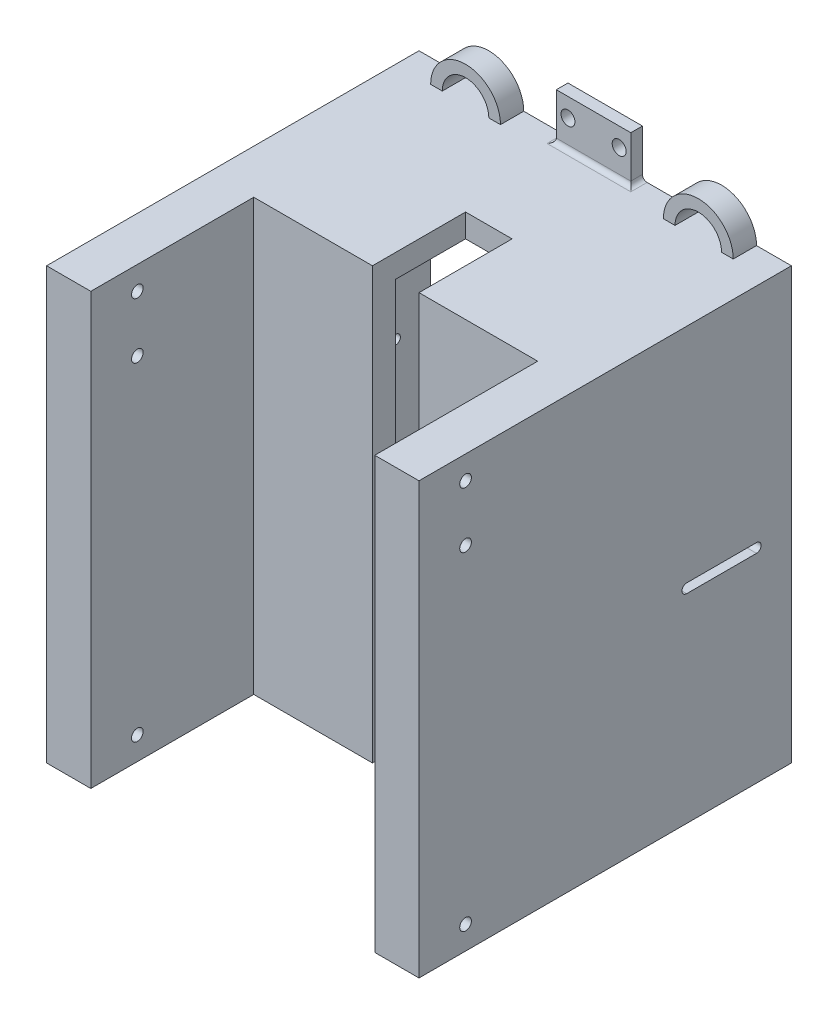
SolidWorks part; units mm, degrees
ref_plane "前基準面" through (0, 0, 0) normal (0, 0, 1) x (1, 0, 0)
ref_plane "上基準面" through (0, 0, 0) normal (0, 1, 0) x (1, 0, 0)
ref_plane "右基準面" through (0, 0, 0) normal (1, 0, 0) x (0, 0, -1)
ref_axis "基準軸1" through (0, -55, 0) along (0, 1, 0)
ref_axis "基準軸2" through (-88.99, 0, 0) along (1, 0, 0)
ref_axis "基準軸3" through (0, 0, 55) along (0, 0, -1)
sketch "草圖1" plane through (0, 0, 0) normal (0, 0, 1) x (1, 0, 0)
  line L1 (-160, -185) -> (0, -185)
  line L2 (-160, -185) -> (-160, 0)
  line L3 (-160, 0) -> (0, 0)
  line L4 (0, -185) -> (0, 0)
  dimension "D1" = 160
  dimension "D2" = 185
extrude "填料-伸長1" add sketch "草圖1" along normal blind 10
sketch "草圖2" plane through (0, 0, 0) normal (0, 0, -1) x (-1, 0, 0)
  line L0 (160, -185) -> (0, -185) construction
  line L2 (0, 0) -> (0, -185)
  line L3 (0, -185) -> (5, -185)
  line L4 (5, -10) -> (5, -185)
  line L5 (55, 0) -> (-55, 0) construction
  line L7 (160, 0) -> (160, -185)
  line L8 (160, -185) -> (155, -185)
  line L9 (155, -10) -> (155, -185)
  line L10 (160, 0) -> (160, -185) construction
  line L11 (5, -10) -> (155, -10)
  line L12 (0, 0) -> (160, 0)
  dimension "D1" = 5
  dimension "D2" = 5
  dimension "D3" = 10
extrude "填料-伸長2" add sketch "草圖2" along normal blind 80
sketch "草圖14" plane through (0, 0, 0) normal (0, 1, 0) x (1, 0, 0)
  line L0 (-80, -10) -> (-80, 74.8376) construction
  line L1 (0, -10) -> (-160, -10) construction
  line L4 (-70, -20) -> (-70, 30)
  line L5 (-70, 30) -> (-90, 30)
  line L6 (-90, -20) -> (-90, 30)
  line L10 (-90, -20) -> (-70, -20)
  point P8 (-80, 30)
  dimension "D1" = 10
  dimension "D2" = 40
  dimension "D3" = 20
extrude "除料-伸長4" cut sketch "草圖14" against normal through all
sketch "草圖16" plane through (0, 0, -80) normal (0, 0, -1) x (-1, 0, 0)
  line L0 (160, 0) -> (0, 0) construction
  line L1 (96, 0) -> (64, 0)
  line L2 (96, 0) -> (96, -10) construction
  line L3 (96, -10) -> (64, -10) construction
  line L4 (64, 0) -> (64, -10) construction
  line L5 (90, -10) -> (155, -10) construction
  line L6 (80, 0) -> (80, -74.9509) construction
  line L7 (64, 0) -> (64, 20)
  line L8 (64, 20) -> (96, 20)
  line L9 (96, 20) -> (96, 0)
  dimension "D1" = 20
  dimension "D2" = 32
extrude "填料-伸長7" add sketch "草圖16" against normal blind 5
sketch "草圖18" plane through (0, 0, -80) normal (0, 0, -1) x (-1, 0, 0)
  line L0 (80, 20) -> (80, -10) construction
  line L1 (96, 20) -> (64, 20) construction
  line L2 (5, -10) -> (155, -10) construction
  line L3 (64, 4) -> (96, 4) construction
  line L4 (64, 20) -> (64, 0) construction
  line L5 (96, 0) -> (96, 20) construction
  line L6 (69, 12) -> (91, 12) construction
  circle A0 centre (69, 12) radius 3
  circle A1 centre (91, 12) radius 3
  point P15 (80, 12)
  dimension "D4" = 6
  dimension "D1" = 16
  dimension "D2" = 11
  dimension "D3" = 8
extrude "除料-伸長7" cut sketch "草圖18" against normal up to next
fillet "圓角1" radius 2 3 edges at (-64, 0, -77.5) (-80, 0, -75) (-96, 0, -77.5)
sketch "草圖21" plane through (-160, 0, 0) normal (-1, 0, 0) x (0, 0, 1)
  line L11 (10, 0) -> (80, 0)
  line L12 (80, 0) -> (80, -185)
  line L13 (80, -185) -> (10, -185)
  line L14 (10, 0) -> (10, -185) construction
  line L15 (10, 0) -> (10, -185)
  circle A1 centre (60, -10) radius 2.5
  circle A2 centre (60, -175) radius 2.5
  circle A3 centre (60, -34) radius 2.5
  dimension "D5" = 70
  dimension "D3" = 10
  dimension "D4" = 5
  dimension "D6" = 24
  dimension "D7" = 5
  dimension "D1" = 10
  dimension "D2" = 50
extrude "填料-伸長8" add sketch "草圖21" against normal up to surface (160 mm away) up to face at (0, -92.5, -35)
sketch "草圖22" plane through (-155, 0, 0) normal (1, 0, 0) x (0, 0, -1)
  line L0 (0, -97.5) -> (80, -97.5) construction
  line L1 (35, -97.5) -> (65, -97.5) construction
  line L2 (35, -95.5) -> (65, -95.5)
  line L3 (35, -99.5) -> (65, -99.5)
  line L4 (0, -10) -> (0, -185)
  line L5 (0, -185) -> (80, -185)
  line L6 (80, -185) -> (80, -10)
  line L7 (80, -10) -> (0, -10)
  line L8 (0, -10) -> (0, -185) construction
  line L9 (0, -185) -> (80, -185) construction
  line L10 (80, -185) -> (80, -10) construction
  line L11 (80, -10) -> (0, -10) construction
  arc A0 (35, -95.5) -> (35, -99.5) centre (35, -97.5) ccw
  arc A1 (65, -99.5) -> (65, -95.5) centre (65, -97.5) ccw
  point P8 (50, -97.5)
  dimension "D3" = 2
  dimension "D2" = 30
  dimension "D4" = 30
  dimension "D1" = 0
extrude "除料-伸長9" cut sketch "草圖22" against normal through all both and the other way through all contours L3 A1 L2 A0
sketch "草圖23" plane through (0, 0, 0) normal (0, 1, 0) x (1, 0, 0)
  line L0 (0, -80) -> (-160, -80) construction
  line L1 (-19, -80) -> (-141, -80)
  line L2 (-19, -80) -> (-19, -10)
  line L3 (-19, -10) -> (-141, -10)
  line L4 (-141, -80) -> (-141, -10)
  line L5 (-160, -80) -> (-160, 80) construction
  line L6 (-70, -10) -> (-90, -10) construction
  line L7 (0, -80) -> (0, 80) construction
  dimension "D1" = 19
  dimension "D2" = 19
extrude "除料-伸長10" cut sketch "草圖23" against normal through all
sketch "草圖24" plane through (0, 0, -80) normal (0, 0, -1) x (-1, 0, 0)
  line L0 (80, 20) -> (80, -221.629) construction
  line L1 (96, 20) -> (64, 20) construction
  line L2 (15, 0) -> (20, 0)
  line L3 (62, 0) -> (0, 0) construction
  line L5 (20, 0) -> (40, 0) construction
  line L6 (15.8579, -5) -> (44.1421, -5) construction
  line L7 (40, 0) -> (45, 0)
  line L8 (120, 0) -> (115, 0)
  line L9 (145, 0) -> (140, 0)
  arc A0 (20, 0) -> (40, 0) centre (30, 0) cw
  arc A1 (15, 0) -> (45, 0) centre (30, 0) cw
  arc A2 (15.8579, -5) -> (44.1421, -5) centre (30, 0) cw construction
  arc A3 (145, 0) -> (115, 0) centre (130, 0) ccw
  arc A4 (140, 0) -> (120, 0) centre (130, 0) ccw
  point P14 (15.5074, 0)
  dimension "D1" = 5
  dimension "D2" = 10
  dimension "D3" = 50
extrude "填料-伸長9" add sketch "草圖24" against normal blind 10
